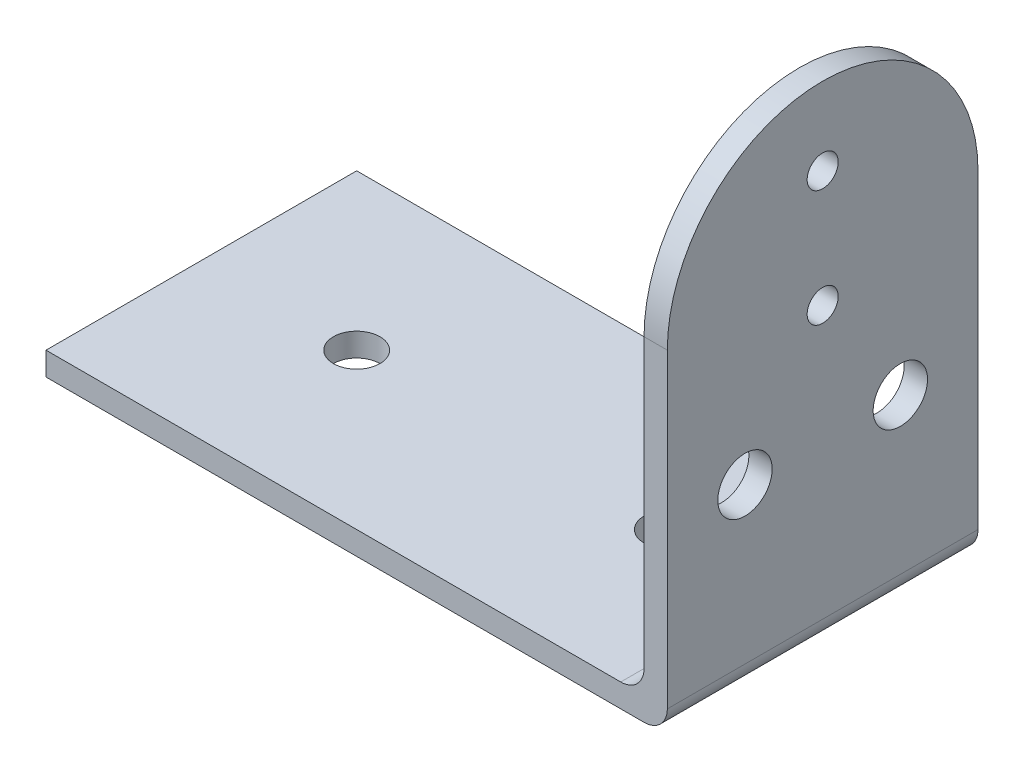
SolidWorks part; units mm, degrees
ref_plane "Front Plane" through (0, 0, 0) normal (0, 0, 1) x (1, 0, 0)
ref_plane "Top Plane" through (0, 0, 0) normal (0, 1, 0) x (1, 0, 0)
ref_plane "Right Plane" through (0, 0, 0) normal (1, 0, 0) x (0, 0, -1)
sketch "Sketch2" plane through (0, 0, 0) normal (0, 1, 0) x (1, 0, 0)
  line L1 (0, 0) -> (80, 0)
  line L2 (0, 0) -> (0, 40)
  line L3 (0, 40) -> (80, 40)
  line L4 (80, 0) -> (80, 40)
  line L5 (80, 40) -> (77, 40)
  line L6 (80, 40) -> (80, 0)
  line L7 (80, 0) -> (77, 0)
  line L8 (77, 40) -> (77, 0)
  dimension "D1" = 40
  dimension "D2" = 80
  dimension "D3" = 3
extrude "Boss-Extrude1" add sketch "Sketch2" against normal blind 3 contours L8 L3 L2 L1 | L3 L8 L1 L4 region at (38.5, 0, -20) region at (78.5, 0, -20)
extrude "Boss-Extrude2" add sketch "Sketch2<3>" along normal blind 60 contours L3 L8 L1 L4 region at (78.5, 0, -20)
sketch "Sketch2<3>" plane through (0, 0, 0) normal (0, 1, 0) x (1, 0, 0) same geometry as "Sketch2"
fillet "Fillet1" radius 3 2 edges at (80, -3, -20) (77, 0, -20)
sketch "Sketch3" plane through (80, 0, 0) normal (1, 0, 0) x (0, 0, -1)
  line L0 (20, 60) -> (20, 0) construction
  line L1 (20, 60) -> (0, 60)
  line L2 (0, 0) -> (40, 0) construction
  line L3 (0, 60) -> (40, 60) construction
  line L4 (0, 60) -> (0, 40)
  line L6 (40, 40) -> (40, 60)
  line L7 (40, 60) -> (20, 60)
  circle A0 centre (20, 50) radius 2
  circle A1 centre (20, 35) radius 2
  arc A2 (40, 40) -> (0, 40) centre (20, 40) ccw
  circle A3 centre (10, 20) radius 3.5
  circle A4 centre (30, 20) radius 3.5
  point P6 (20, 0)
  line M3 (0, 60) -> (0, 0)
  line M5 (40, 0) -> (40, 60)
  line M6 (40, 60) -> (0, 60)
  dimension "D1" = 4
  dimension "D4" = 4
  dimension "D8" = 7
  dimension "D2" = 10
  dimension "D3" = 15
  dimension "D5" = 20
  dimension "D6" = 10
  dimension "D7" = 20
extrude "Cut-Extrude1" cut sketch "Sketch3" against normal through all contours A3 | A4 | L0 A1 | A1 L0 | A0 L0 | L0 A0 | A2 M6 M3 | A2 M5 M6 region at (80, 35, -20.8488) region at (80, 35, -19.1512) region at (80, 50, -20.8488) region at (80, 50, -19.1512) region at (80, 55.5326, -4.4674) region at (80, 55.5326, -35.5326) region at (80, 20, -10) region at (80, 20, -30)
sketch "Sketch7" plane through (0, -3, 0) normal (0, -1, 0) x (1, 0, 0)
  line L0 (-5.2653, -20) -> (83.8713, -20) construction
  line L1 (0, 0) -> (77, 0) construction
  line L4 (80, 0) -> (80, -40) construction
  line L5 (0, 0) -> (0, -40) construction
  circle A0 centre (60, -20) radius 3
  circle A1 centre (20, -20) radius 3
  dimension "D3" = 6
  dimension "D5" = 6
  dimension "D1" = 20
  dimension "D2" = 20
  dimension "D4" = 20
  dimension "D6" = 40
extrude "Cut-Extrude2" cut sketch "Sketch7" against normal through all contours A1 | A0
